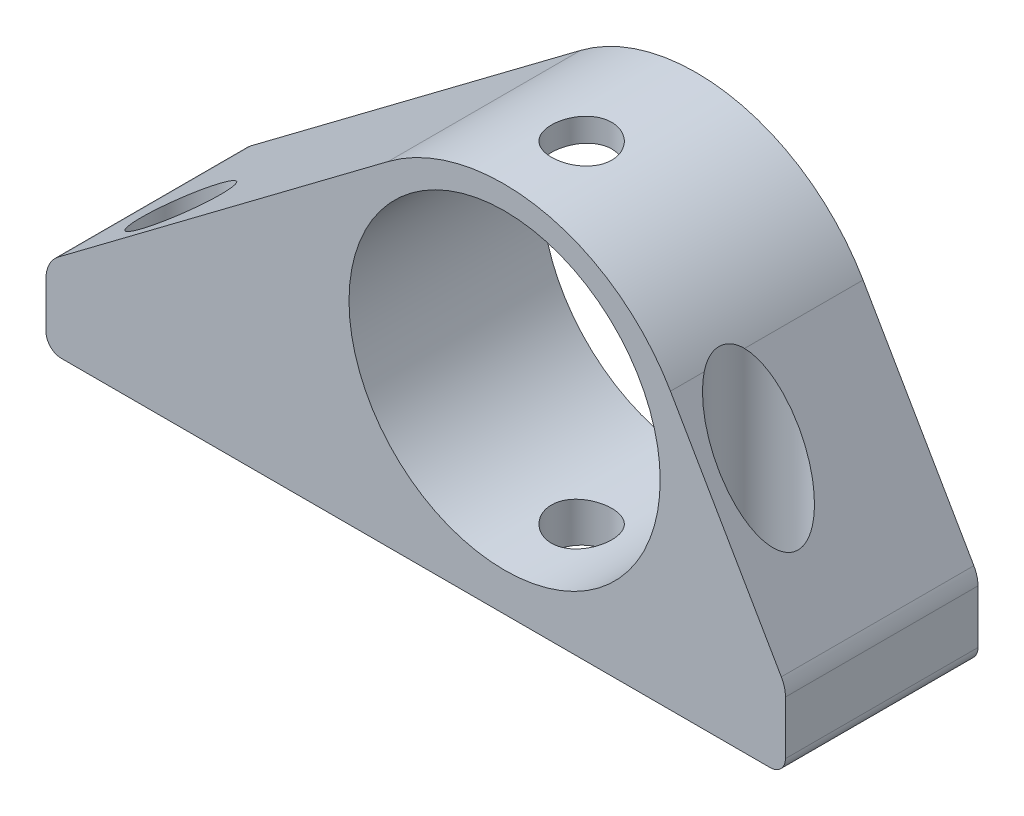
SolidWorks part; units mm, degrees
ref_plane "Alzado" through (0, 0, 0) normal (0, 0, 1) x (1, 0, 0)
ref_plane "Planta" through (0, 0, 0) normal (0, 1, 0) x (1, 0, 0)
ref_plane "Vista lateral" through (0, 0, 0) normal (1, 0, 0) x (0, 0, -1)
sketch "Croquis1" plane through (0, 0, 0) normal (0, 0, 1) x (1, 0, 0)
  line L4 (30.48, 0) -> (-30.48, 0)
  line L5 (-30.48, 0) -> (-30.48, 6.35)
  line L6 (-30.48, 6.35) -> (12.0465, 38.2778)
  line L7 (12.0465, 38.2778) -> (30.48, 6.35)
  line L8 (30.48, 6.35) -> (30.48, 0)
  line L9 (0, 0) -> (0, 44.0233) construction
  point P11 (0, 0)
  dimension "D1" = 6.35
  dimension "D2" = 38.2778
  dimension "D3" = 60.96
  dimension "D4" = 30
extrude "Saliente-Extruir1" add sketch "Croquis1" along normal blind 15.875
fillet "Redondeo1" radius 15.875 1 edges at (12.0465, 38.2778, 7.9375)
sketch "Croquis2" plane through (0, 0, 15.875) normal (0, 0, 1) x (1, 0, 0)
  line L0 (30.48, 6.35) -> (21.0022, 22.7661) construction
  circle A0 centre (7.3273, 15.9716) radius 9.652
  arc A1 (21.0022, 22.7661) -> (-2.2773, 27.5239) centre (7.254, 14.8286) ccw construction
  dimension "D1" = 5.08
  dimension "D2" = 19.304
  dimension "D3" = 15.24
extrude "Cortar-Extruir1" cut sketch "Croquis2" against normal up to next
sketch "Croquis3" plane through (0, 0, 15.875) normal (0, 0, 1) x (1, 0, 0)
  circle A0 centre (7.3273, 15.9716) radius 12.827
  dimension "D1" = 25.654
extrude "Cortar-Extruir2" cut sketch "Croquis3" against normal through all
sketch "Croquis4" plane through (0, 0, 0) normal (0, -1, 0) x (1, 0, 0)
  line L0 (-30.48, 15.875) -> (-30.48, 0) construction
  line L1 (-30.48, 15.875) -> (30.48, 15.875) construction
  line L2 (0, 0) -> (0, 12.065) construction
  line L3 (-30.48, 0) -> (30.48, 0) construction
  line L5 (20.1543, 15.875) -> (-5.4997, 15.875) construction
  line L6 (20.1543, 15.875) -> (-5.4997, 15.875)
  circle A0 centre (-23.8125, 11.43) radius 3.2639
  circle A1 centre (23.8125, 11.43) radius 3.2639
  circle A3 centre (7.3273, 9.525) radius 2.4892
  point P21 (7.3273, 15.875)
  dimension "D1" = 6.5278
  dimension "D4" = 4.9784
  dimension "D5" = 6.35
  dimension "D2" = 6.6675
  dimension "D3" = 4.445
extrude "Cortar-Extruir3" cut sketch "Croquis4" against normal through all contours A3 | A0 | A1
fillet "Redondeo2" radius 2.54 2 edges at (-30.48, 6.35, 7.9375) (30.48, 6.35, 7.9375)
fillet "Redondeo3" radius 1.27 2 edges at (30.48, 0, 7.9375) (-30.48, 0, 7.9375)
